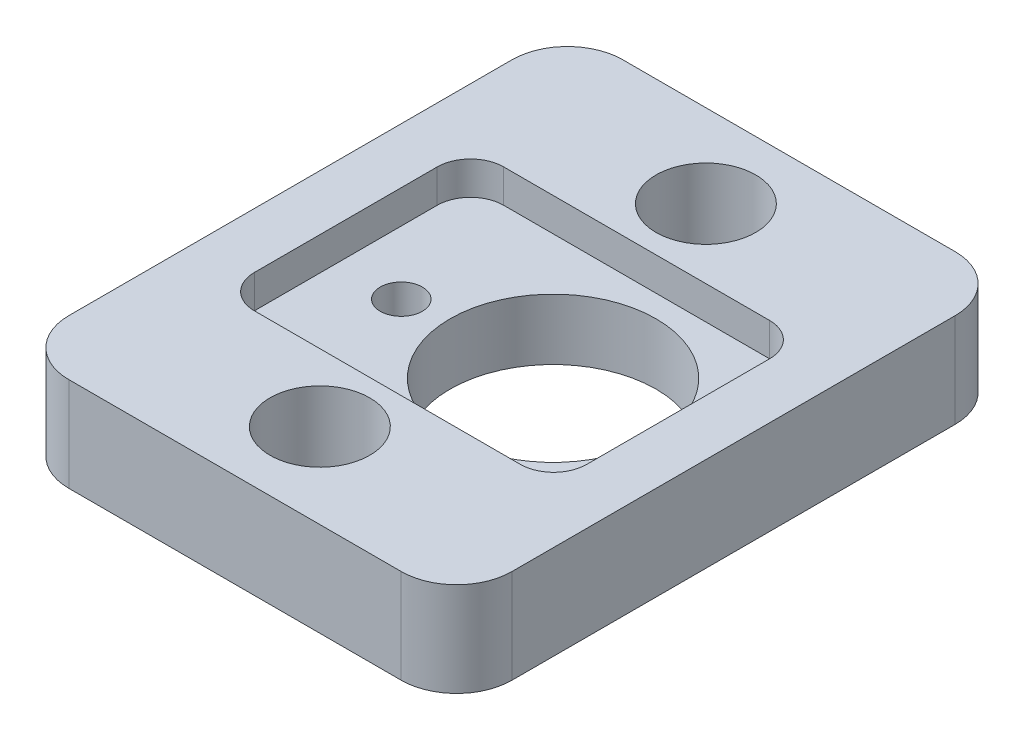
SolidWorks part; units mm, degrees
ref_plane "Front Plane" through (0, 0, 0) normal (0, 0, 1) x (1, 0, 0)
ref_plane "Top Plane" through (0, 0, 0) normal (0, 1, 0) x (1, 0, 0)
ref_plane "Right Plane" through (0, 0, 0) normal (1, 0, 0) x (0, 0, -1)
sketch "Sketch1" plane through (0, 0, 0) normal (0, 1, 0) x (1, 0, 0)
  line L1 (2, 0) -> (14, 0)
  line L2 (0, -2) -> (0, -18)
  line L3 (2, -20) -> (14, -20)
  line L4 (16, -2) -> (16, -18)
  arc A0 (0, -18) -> (2, -20) centre (2, -18) ccw
  arc A1 (14, -20) -> (16, -18) centre (14, -18) ccw
  arc A2 (14, 0) -> (16, -2) centre (14, -2) cw
  arc A3 (2, 0) -> (0, -2) centre (2, -2) ccw
  point P7 (0, -20)
  point P12 (16, 0)
  point P15 (0, 0)
  dimension "D3" = 2
  dimension "D1" = 16
  dimension "D2" = 20
extrude "Boss-Extrude1" add sketch "Sketch1" along normal blind 3.4
sketch "Sketch2" plane through (0, 3.4, 0) normal (0, 1, 0) x (1, 0, 0)
  line L0 (14, 0) -> (2, 0) construction
  line L1 (3.2, -5.5) -> (12.8, -5.5)
  line L2 (2, -6.7) -> (2, -13.3)
  line L3 (3.2, -14.5) -> (12.8, -14.5)
  line L4 (14, -6.7) -> (14, -13.3)
  line L5 (16, -18) -> (16, -2) construction
  arc A0 (2, -13.3) -> (3.2, -14.5) centre (3.2, -13.3) ccw
  arc A1 (12.8, -14.5) -> (14, -13.3) centre (12.8, -13.3) ccw
  arc A2 (12.8, -5.5) -> (14, -6.7) centre (12.8, -6.7) cw
  arc A3 (3.2, -5.5) -> (2, -6.7) centre (3.2, -6.7) ccw
  point P4 (8, -5.5)
  point P9 (2, -14.5)
  point P14 (14, -5.5)
  point P17 (2, -5.5)
  dimension "D4" = 1.2
  dimension "D1" = 12
  dimension "D2" = 9
  dimension "D3" = 5.5
  dimension "D5" = 2
extrude "Cut-Extrude1" cut sketch "Sketch2" against normal blind 1.2
sketch "Sketch3" plane through (0, 2.2, 0) normal (0, 1, 0) x (1, 0, 0)
  line L0 (14, -13.3) -> (14, -6.7) construction
  circle A0 centre (9.5, -10.0174) radius 3.72
  point P2 (9.5, -9.7767)
  point P3 (9.5, -10.0174)
  dimension "D1" = 7.44
  dimension "D2" = 4.5
extrude "Cut-Extrude2" cut sketch "Sketch3" against normal through all
sketch "Sketch4" plane through (0, 3.4, 0) normal (0, 1, 0) x (1, 0, 0)
  line L1 (0, -2) -> (0, -18) construction
  line L2 (14, 0) -> (2, 0) construction
  circle A0 centre (8, -3) radius 1.8
  circle A2 centre (8, -16.9366) radius 1.8
  point P0 (8, -16.9366)
  dimension "D1" = 3
  dimension "D2" = 8
extrude "Cut-Extrude3" cut sketch "Sketch4" against normal through all
sketch "Sketch5" plane through (0, 2.2, 0) normal (0, 1, 0) x (1, 0, 0)
  circle A0 centre (4.2868, -10.2839) radius 0.76
  circle A1 centre (9.5, -10.0174) radius 3.72 construction
  dimension "D1" = 1.5
  dimension "D2" = 1.52
extrude "Cut-Extrude4" cut sketch "Sketch5" against normal blind 10
